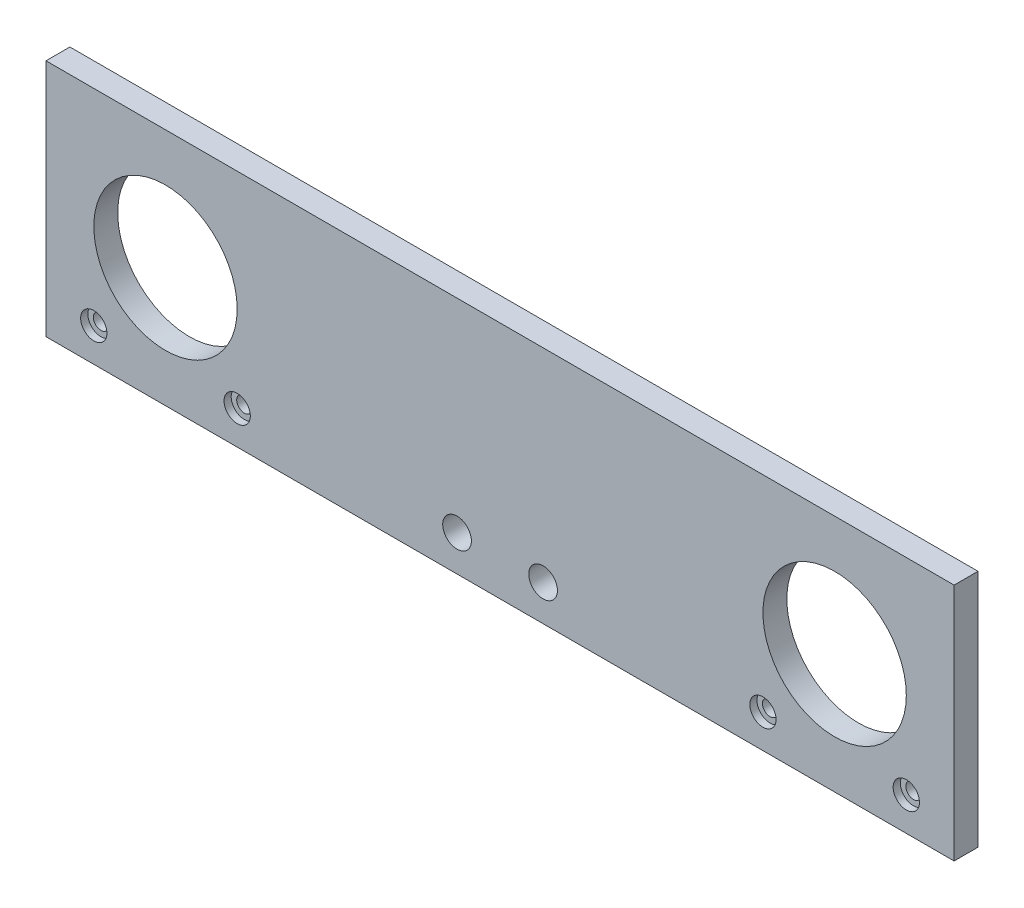
SolidWorks part; units mm, degrees
ref_plane "Front Plane" through (0, 0, 0) normal (0, 0, 1) x (1, 0, 0)
ref_plane "Top Plane" through (0, 0, 0) normal (0, 1, 0) x (1, 0, 0)
ref_plane "Right Plane" through (0, 0, 0) normal (1, 0, 0) x (0, 0, -1)
sketch "Sketch1" plane through (0, 0, 0) normal (0, 0, 1) x (1, 0, 0)
  line L1 (0, 0) -> (190, 0)
  line L2 (0, 0) -> (0, 50)
  line L3 (0, 50) -> (190, 50)
  line L4 (190, 0) -> (190, 50)
  circle A0 centre (25, 25) radius 15
  circle A1 centre (165, 25) radius 15
  circle A2 centre (40, 7) radius 1.6
  circle A3 centre (180, 7) radius 1.6
  circle A4 centre (150, 7) radius 1.6
  circle A5 centre (10, 7) radius 1.6
  circle A6 centre (86, 7.5) radius 3
  circle A7 centre (104, 7.5) radius 3
  point P5 (95, 25)
  dimension "D3" = 30
  dimension "D7" = 30
  dimension "D9" = 3.2
  dimension "D11" = 15
  dimension "D15" = 3.2
  dimension "D16" = 7
  dimension "D23" = 6
  dimension "D24" = 6
  dimension "D12" = 7
  dimension "D14" = 3.2
  dimension "D18" = 3.2
  dimension "D2" = 50
  dimension "D4" = 70
  dimension "D5" = 95
  dimension "D6" = 25
  dimension "D8" = 70
  dimension "D10" = 15
  dimension "D13" = 7
  dimension "D17" = 15
  dimension "D20" = 7
  dimension "D21" = 25
  dimension "D22" = 25
  dimension "D25" = 7.5
  dimension "D26" = 7.5
  dimension "D27" = 9
  dimension "D32" = 95
  dimension "D35" = 9
extrude "Boss-Extrude1" add sketch "Sketch1" along normal blind 5 contours L3 L2 L1 A2 A0 | L1 L4 L3 A4 A1 region at (95, 25.1961, 0)
sketch "Sketch3" plane through (0, 0, 5) normal (0, 0, 1) x (1, 0, 0)
  circle A0 centre (10, 7) radius 2.75
  circle A1 centre (40, 7) radius 2.75
  circle A2 centre (150, 7) radius 2.75
  circle A3 centre (180, 7) radius 2.75
  dimension "D1" = 5.5
extrude "Cut-Extrude1" cut sketch "Sketch3" against normal blind 1.5 contours A0 | A1 | A2 | A3
